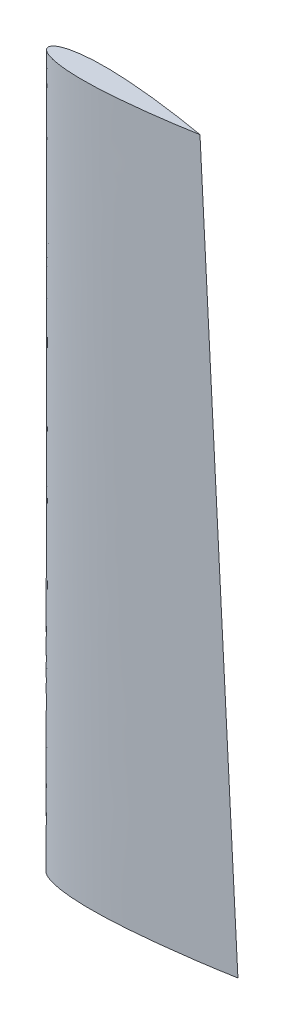
SolidWorks part; units mm, degrees
material "Polyurethane Foam Rigid"
ref_plane "Front Plane" through (0, 0, 0) normal (0, 0, 1) x (1, 0, 0)
ref_plane "Top Plane" through (0, 0, 0) normal (0, 1, 0) x (1, 0, 0)
ref_plane "Right Plane" through (0, 0, 0) normal (1, 0, 0) x (0, 0, -1)
sketch "rootSketch" plane through (0, 0, 0) normal (0, 1, 0) x (1, 0, 0)
  line L0 (0, 0) -> (1500, 0) construction
  line L2 (13, -3.9) -> (13, 3.9) construction
  line L3 (0, 0) -> (52, 0) construction
  spline S0 degree 4 poles (0, 0) (0, 0.0566) (0.0054, 0.148) (0.0261, 0.2802) (0.0778, 0.4522) (0.1471, 0.6119) (0.2485, 0.786) (0.3924, 0.9775) (0.5992, 1.1954) (0.9058, 1.4518) (1.3705, 1.7579) (2.0783, 2.1191) (3.1757, 2.542) (4.8233, 2.9987) (7.2754, 3.453) (10.4387, 3.7805) (14.1293, 3.9293) (18.1436, 3.8963) (22.1517, 3.7223) (25.6562, 3.476) (28.6515, 3.2136) (31.6507, 2.914) (34.1342, 2.6396) (36.6395, 2.3366) (39.5995, 1.9537) (42.1279, 1.6007) (44.5332, 1.2475) (47.1211, 0.8374) (48.9103, 0.5455) (51.4233, 0.1075) (52.8542, -0.154) (54.9428, -0.5501) (55.9597, -0.7584) (56.7861, -0.9233) (56.9961, -0.9696) (57.2092, -1.0126) knots 0 0 0 0 0 0.003841 0.006235 0.009072 0.012193 0.015657 0.019917 0.025339 0.032593 0.042799 0.057705 0.079311 0.112503 0.158973 0.227236 0.2955 0.363764 0.432028 0.500292 0.534424 0.568556 0.63682 0.670952 0.705084 0.773347 0.807479 0.841611 0.875743 0.909875 0.954938 0.977469 0.988734 1 1 1 1 1 construction
  spline S1 degree 4 poles (0, 0) (0, 0.0566) (0.0054, 0.148) (0.0261, 0.2802) (0.0778, 0.4522) (0.1471, 0.6119) (0.2485, 0.786) (0.3924, 0.9775) (0.5992, 1.1954) (0.9058, 1.4518) (1.3705, 1.7579) (2.0783, 2.1191) (3.1757, 2.542) (4.8233, 2.9987) (7.2754, 3.453) (10.4387, 3.7805) (14.1293, 3.9293) (18.1436, 3.8963) (22.1517, 3.7223) (25.6562, 3.476) (28.6515, 3.2136) (31.6507, 2.914) (34.1342, 2.6396) (36.6395, 2.3366) (39.5995, 1.9537) (42.1279, 1.6007) (44.5332, 1.2475) (47.1211, 0.8374) (48.9103, 0.5455) (50.6553, 0.2414) (51.551, 0.0816) (52, 0) knots 0 0 0 0 0 0.003841 0.006235 0.009072 0.012193 0.015657 0.019917 0.025339 0.032593 0.042799 0.057705 0.079311 0.112503 0.158973 0.227236 0.2955 0.363764 0.432028 0.500292 0.534424 0.568556 0.63682 0.670952 0.705084 0.773347 0.807479 0.841611 0.875743 0.909875 0.909875 0.909875 0.909875 0.909875
  spline S2 degree 4 poles (0, 0) (0, -0.0566) (0.0054, -0.148) (0.0261, -0.2802) (0.0778, -0.4522) (0.1471, -0.6119) (0.2485, -0.786) (0.3924, -0.9775) (0.5992, -1.1954) (0.9058, -1.4518) (1.3705, -1.7579) (2.0783, -2.1191) (3.1757, -2.542) (4.8233, -2.9987) (7.2754, -3.453) (10.4387, -3.7805) (14.1293, -3.9293) (18.1436, -3.8963) (22.1517, -3.7223) (25.6562, -3.476) (28.6515, -3.2136) (31.6507, -2.914) (34.1342, -2.6396) (36.6395, -2.3366) (39.5995, -1.9537) (42.1279, -1.6007) (44.5332, -1.2475) (47.1211, -0.8374) (48.9103, -0.5455) (51.4233, -0.1075) (52.8542, 0.154) (54.9428, 0.5501) (55.9597, 0.7584) (56.7861, 0.9233) (56.9961, 0.9696) (57.2092, 1.0126) knots 0 0 0 0 0 0.003841 0.006235 0.009072 0.012193 0.015657 0.019917 0.025339 0.032593 0.042799 0.057705 0.079311 0.112503 0.158973 0.227236 0.2955 0.363764 0.432028 0.500292 0.534424 0.568556 0.63682 0.670952 0.705084 0.773347 0.807479 0.841611 0.875743 0.909875 0.954938 0.977469 0.988734 1 1 1 1 1 construction
  spline S3 degree 4 poles (0, 0) (0, -0.0566) (0.0054, -0.148) (0.0261, -0.2802) (0.0778, -0.4522) (0.1471, -0.6119) (0.2485, -0.786) (0.3924, -0.9775) (0.5992, -1.1954) (0.9058, -1.4518) (1.3705, -1.7579) (2.0783, -2.1191) (3.1757, -2.542) (4.8233, -2.9987) (7.2754, -3.453) (10.4387, -3.7805) (14.1293, -3.9293) (18.1436, -3.8963) (22.1517, -3.7223) (25.6562, -3.476) (28.6515, -3.2136) (31.6507, -2.914) (34.1342, -2.6396) (36.6395, -2.3366) (39.5995, -1.9537) (42.1279, -1.6007) (44.5332, -1.2475) (47.1211, -0.8374) (48.9103, -0.5455) (50.6553, -0.2414) (51.551, -0.0816) (52, 0) knots 0 0 0 0 0 0.003841 0.006235 0.009072 0.012193 0.015657 0.019917 0.025339 0.032593 0.042799 0.057705 0.079311 0.112503 0.158973 0.227236 0.2955 0.363764 0.432028 0.500292 0.534424 0.568556 0.63682 0.670952 0.705084 0.773347 0.807479 0.841611 0.875743 0.909875 0.909875 0.909875 0.909875 0.909875
  point P10 (13, 0)
  dimension "incidenceAngle" = 0
  dimension "rootChord" = 52
  dimension "rootQuarterChord" = 13
  dimension "rootMaxThickness" = 7.8
ref_plane "Plane1" through (0, 195.0016, 0) normal (0, 1, 0) x (1, 0, 0)
sketch "tipSketch" plane through (0, 195.0016, 0) normal (0, 1, 0) x (1, 0, 0)
  line L0 (216.8234, 0) -> (518.1352, 0) construction
  line L3 (0, 0) -> (41.6, 0) construction
  line L4 (10.4, -3.12) -> (10.4, 3.12) construction
  spline S0 degree 4 poles (0, 0) (0, 0.0453) (0.0043, 0.1184) (0.0209, 0.2242) (0.0622, 0.3618) (0.1176, 0.4895) (0.1988, 0.6288) (0.3139, 0.782) (0.4793, 0.9563) (0.7247, 1.1615) (1.0964, 1.4063) (1.6626, 1.6953) (2.5406, 2.0336) (3.8586, 2.399) (5.8203, 2.7624) (8.3509, 3.0244) (11.3035, 3.1434) (14.5149, 3.117) (17.7214, 2.9778) (20.525, 2.7808) (22.9212, 2.5709) (25.3206, 2.3312) (27.3073, 2.1117) (29.3116, 1.8693) (31.6796, 1.5629) (33.7024, 1.2806) (35.6266, 0.998) (37.6969, 0.6699) (39.1283, 0.4364) (41.1386, 0.086) (42.2833, -0.1232) (43.9542, -0.4401) (44.7678, -0.6067) (45.4289, -0.7386) (45.5969, -0.7757) (45.7674, -0.8101) knots 0 0 0 0 0 0.003841 0.006235 0.009072 0.012193 0.015657 0.019917 0.025339 0.032593 0.042799 0.057705 0.079311 0.112503 0.158973 0.227236 0.2955 0.363764 0.432028 0.500292 0.534424 0.568556 0.63682 0.670952 0.705084 0.773347 0.807479 0.841611 0.875743 0.909875 0.954938 0.977469 0.988734 1 1 1 1 1 construction
  spline S1 degree 4 poles (0, 0) (0, 0.0453) (0.0043, 0.1184) (0.0209, 0.2242) (0.0622, 0.3618) (0.1176, 0.4895) (0.1988, 0.6288) (0.3139, 0.782) (0.4793, 0.9563) (0.7247, 1.1615) (1.0964, 1.4063) (1.6626, 1.6953) (2.5406, 2.0336) (3.8586, 2.399) (5.8203, 2.7624) (8.3509, 3.0244) (11.3035, 3.1434) (14.5149, 3.117) (17.7214, 2.9778) (20.525, 2.7808) (22.9212, 2.5709) (25.3206, 2.3312) (27.3073, 2.1117) (29.3116, 1.8693) (31.6796, 1.5629) (33.7024, 1.2806) (35.6266, 0.998) (37.6969, 0.6699) (39.1283, 0.4364) (40.5243, 0.1931) (41.2408, 0.0653) (41.6, 0) knots 0 0 0 0 0 0.003841 0.006235 0.009072 0.012193 0.015657 0.019917 0.025339 0.032593 0.042799 0.057705 0.079311 0.112503 0.158973 0.227236 0.2955 0.363764 0.432028 0.500292 0.534424 0.568556 0.63682 0.670952 0.705084 0.773347 0.807479 0.841611 0.875743 0.909875 0.909875 0.909875 0.909875 0.909875
  spline S2 degree 4 poles (0, 0) (0, -0.0453) (0.0043, -0.1184) (0.0209, -0.2242) (0.0622, -0.3618) (0.1176, -0.4895) (0.1988, -0.6288) (0.3139, -0.782) (0.4793, -0.9563) (0.7247, -1.1615) (1.0964, -1.4063) (1.6626, -1.6953) (2.5406, -2.0336) (3.8586, -2.399) (5.8203, -2.7624) (8.3509, -3.0244) (11.3035, -3.1434) (14.5149, -3.117) (17.7214, -2.9778) (20.525, -2.7808) (22.9212, -2.5709) (25.3206, -2.3312) (27.3073, -2.1117) (29.3116, -1.8693) (31.6796, -1.5629) (33.7024, -1.2806) (35.6266, -0.998) (37.6969, -0.6699) (39.1283, -0.4364) (41.1386, -0.086) (42.2833, 0.1232) (43.9542, 0.4401) (44.7678, 0.6067) (45.4289, 0.7386) (45.5969, 0.7757) (45.7674, 0.8101) knots 0 0 0 0 0 0.003841 0.006235 0.009072 0.012193 0.015657 0.019917 0.025339 0.032593 0.042799 0.057705 0.079311 0.112503 0.158973 0.227236 0.2955 0.363764 0.432028 0.500292 0.534424 0.568556 0.63682 0.670952 0.705084 0.773347 0.807479 0.841611 0.875743 0.909875 0.954938 0.977469 0.988734 1 1 1 1 1 construction
  spline S3 degree 4 poles (0, 0) (0, -0.0453) (0.0043, -0.1184) (0.0209, -0.2242) (0.0622, -0.3618) (0.1176, -0.4895) (0.1988, -0.6288) (0.3139, -0.782) (0.4793, -0.9563) (0.7247, -1.1615) (1.0964, -1.4063) (1.6626, -1.6953) (2.5406, -2.0336) (3.8586, -2.399) (5.8203, -2.7624) (8.3509, -3.0244) (11.3035, -3.1434) (14.5149, -3.117) (17.7214, -2.9778) (20.525, -2.7808) (22.9212, -2.5709) (25.3206, -2.3312) (27.3073, -2.1117) (29.3116, -1.8693) (31.6796, -1.5629) (33.7024, -1.2806) (35.6266, -0.998) (37.6969, -0.6699) (39.1283, -0.4364) (40.5243, -0.1931) (41.2408, -0.0653) (41.6, 0) knots 0 0 0 0 0 0.003841 0.006235 0.009072 0.012193 0.015657 0.019917 0.025339 0.032593 0.042799 0.057705 0.079311 0.112503 0.158973 0.227236 0.2955 0.363764 0.432028 0.500292 0.534424 0.568556 0.63682 0.670952 0.705084 0.773347 0.807479 0.841611 0.875743 0.909875 0.909875 0.909875 0.909875 0.909875
  point P10 (10.4, 0)
  dimension "incidenceAngle" = 0
  dimension "tipChord" = 41.6
  dimension "tipQuarterChord" = 10.4
  dimension "tipMaxThickness" = 6.24
  dimension "sweepOffset" = 0
loft "Loft1" add profiles "rootSketch", "tipSketch" connector at (0, 0, 0) connector at (0, 195.0016, 0)
ref_plane "Plane2" through (52, 0, 0) normal (1, 0, 0) x (0, 0, -1)
sketch "rudderSketch" plane through (0, 0, 0) normal (0, 0, 1) x (1, 0, 0)
  line L0 (0, 0) -> (0, 48.7504) construction
  line L1 (0, 0) -> (0, 146.2512) construction
  line L2 (0, 48.7504) -> (24.7, 48.7504) construction
  line L3 (0, 146.2512) -> (24.7, 146.2512) construction
  line L4 (24.7, 146.2512) -> (24.7, 48.7504)
  line L5 (24.7, 146.2512) -> (76.7, 146.2512)
  line L6 (24.7, 48.7504) -> (76.7, 48.7504)
  line L7 (76.7, 48.7504) -> (76.7, 146.2512)
  line L8 (76.31, 49.1404) -> (76.31, 145.8612)
  line L9 (25.09, 145.8612) -> (76.31, 145.8612)
  line L10 (25.09, 145.8612) -> (25.09, 49.1404)
  line L11 (25.09, 49.1404) -> (76.31, 49.1404)
  dimension "rudderStartyLoc" = 48.7504
  dimension "rudderEndyLoc" = 146.2512
  dimension "rudderStartxLoc" = 24.7
  dimension "rudderEndeLoc" = 24.7
  dimension "D1" = 52
  dimension "D2" = 52
  dimension "D3" = 0.39
extrude "Cut-Extrude1" [suppressed] cut sketch "rudderSketch" against normal blind 200 and the other way blind 200
equation "\"rootChord@rootSketch\"=(\"rootChord\"+\"rootChord\")/2"
equation "\"incidenceAngle@rootSketch\"=(\"incidentAngle\"+\"incidentAngle\")/2"
equation "\"rootQuarterChord@rootSketch\" = \"rootChord@rootSketch\" / 4"
equation "\"rootMaxThickness@rootSketch\" = \"rootChord\" * \"NACAairfoil\" / 100"
equation "\"halfSpan@Plane1\"= \"rootChord@rootSketch\" * ( 1 + \"taperRatio\" ) / 2 * \"aspectRatio\""
equation "\"incidenceAngle@tipSketch\" = \"incidenceAngle@rootSketch\""
equation "\"tipChord@tipSketch\"= \"rootChord@rootSketch\" * \"taperRatio\""
equation "\"tipQuarterChord@tipSketch\"=\"tipChord@tipSketch\"/4"
equation "\"tipMaxThickness@tipSketch\"=\"tipChord@tipSketch\"*\"NACAairfoil\"/100"
equation "\"rootChord@Plane2\"=\"rootChord@rootSketch\""
equation "\"rudderCenter\"= 0.5'Center of the rudder as a percentage of half span"
equation "\"rudderWidth\"= 0.5'Width of the rudder as a percentage of half span"
equation "\"rudderStartyLoc@rudderSketch\"=\"halfSpan@Plane1\" *  ( \"rudderCenter\" - \"rudderWidth\" / 2 )"
equation "\"rudderEndyLoc@rudderSketch\"=\"halfSpan@Plane1\" *  ( \"rudderCenter\" + \"rudderWidth\" / 2 )"
equation "\"rudderStartxLoc@rudderSketch\"=\"rudderStartyLoc@rudderSketch\"*tan ( \"sweepAngle\" ) + 0.5*(\"rootChord@rootSketch\" + \"rudderStartyLoc@rudderSketch\"*(((\"tipChord@tipSketch\"-\"rootChord@rootSketch\")/\"halfSpan@Plane1\")))"
equation "\"rudderEndeLoc@rudderSketch\"=\"rudderStartyLoc@rudderSketch\"*tan ( \"sweepAngle\" ) + 0.5*(\"rootChord@rootSketch\" + \"rudderStartyLoc@rudderSketch\"*(((\"tipChord@tipSketch\"-\"rootChord@rootSketch\")/\"halfSpan@Plane1\")))"
equation "\"D1@rudderSketch\"=1*\"rootChord@rootSketch\""
equation "\"D2@rudderSketch\"=1*\"rootChord@rootSketch\""
equation "\"D3@rudderSketch\"=\"halfSpan@Plane1\"/500"
equation "\"sweepOffset@tipSketch\" = \"halfSpan@Plane1\" * tan ( \"sweepAngle\" ) "
equation "\"D2@tipSketch\"=\"tipChord@tipSketch\"*tan(\"incidentAngle\")"
equation "\"rootChord\"= 0.052"
equation "\"NACAairfoil\"= 0015"
equation "\"incidentAngle\"= 0"
equation "\"aspectRatio\"= 4.1667"
equation "\"taperRatio\"= 0.8"
equation "\"sweepAngle\"= 0"
